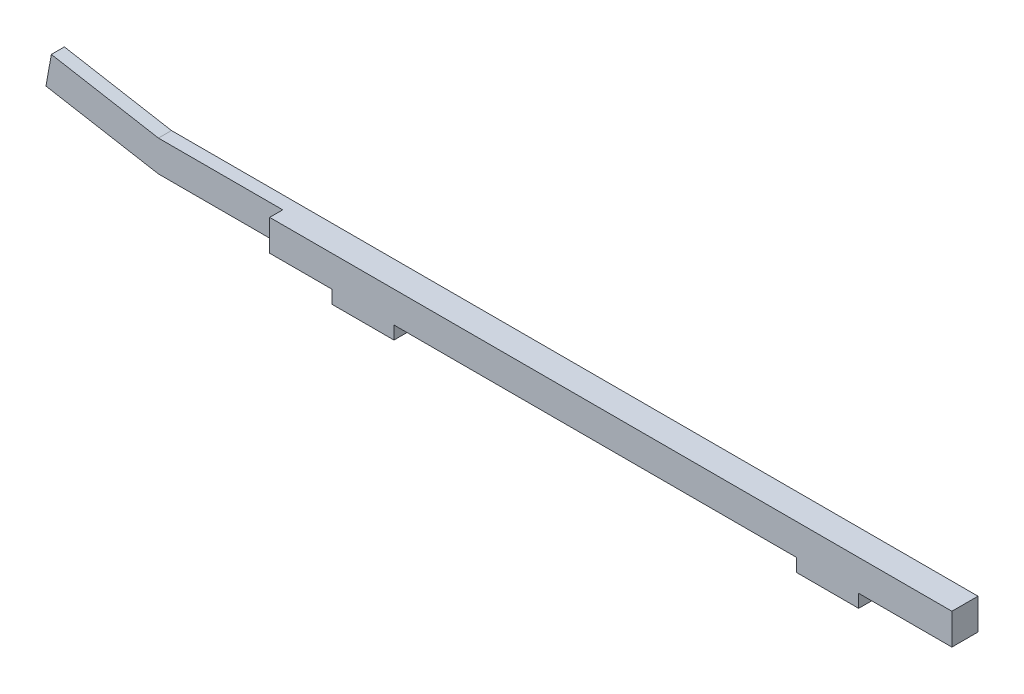
SolidWorks part; units mm, degrees
ref_plane "Front" through (0, 0, 0) normal (0, 0, 1) x (1, 0, 0)
ref_plane "Top" through (0, 0, 0) normal (0, 1, 0) x (1, 0, 0)
ref_plane "Right" through (0, 0, 0) normal (1, 0, 0) x (0, 0, -1)
sketch "Sketch1" plane through (0, 5.334, 0) normal (0, 1, 0) x (1, 0, 0)
  line L0 (266.117, -54.6115) -> (291.517, -54.6115)
  line L1 (76.2, -54.6115) -> (101.6, -54.6115)
  line L2 (76.2, -54.6115) -> (76.2, -65.2795)
  line L3 (76.2, -65.2795) -> (101.6, -65.2795)
  line L4 (101.6, -54.6115) -> (101.6, -65.2795)
  line L5 (266.117, -54.6115) -> (266.117, -65.2795)
  line L6 (266.117, -65.2795) -> (291.517, -65.2795)
  line L7 (291.517, -54.6115) -> (291.517, -65.2795)
  line L8 (380.417, -21.0684) -> (380.417, -97.6337) construction
  line L9 (0, 0) -> (0, -206.442) construction
  line L11 (329.617, -54.6115) -> (0, -54.6115)
  line L12 (329.617, -54.6115) -> (329.617, -65.2795)
  line L13 (329.617, -65.2795) -> (0, -65.2795)
  line L14 (0, -54.6115) -> (0, -65.2795)
  line M10 (0, 0) -> (0, -170.2354)
  dimension "D1" = 25.4
  dimension "D2" = 10.668
  dimension "D4" = 88.9
  dimension "D5" = 76.2
  dimension "D6" = 50.8
  dimension "D3" = 2
extrude "Boss-Extrude1" add sketch "Sketch1" against normal blind 5.334 contours L4 L1 L2 L3 | L7 L0 L5 L6 region at (278.817, 5.334, 59.9455) region at (88.9, 5.334, 59.9455)
extrude "Boss-Extrude2" add sketch "Sketch1<3>" along normal blind 12.7 contours L13 L2 L11 M10 | L4 L1 L2 L3 | L13 L5 L11 L4 | L7 L0 L5 L6 | L11 L14 L13 L12 region at (278.817, 5.334, 59.9455) region at (183.8585, 5.334, 59.9455) region at (88.9, 5.334, 59.9455) region at (38.1, 5.334, 59.9455)
sketch "Sketch1<3>" plane through (0, 5.334, 0) normal (0, 1, 0) x (1, 0, 0) same geometry as "Sketch1"
sketch "Sketch2" plane through (0, 0, 54.6115) normal (0, 0, -1) x (-1, 0, 0)
  line L0 (45.9465, 13.4356) -> (43.7747, 25.7527)
  line L1 (-76.2, 5.334) -> (0, 5.334) construction
  line L13 (0, 5.334) -> (45.9465, 13.4356)
  line L14 (0, 18.034) -> (43.7747, 25.7527)
  line M9 (0, 5.334) -> (0, 18.034)
  dimension "D1" = 10
  dimension "D3" = 44.45
extrude "Dihedral Angle" add sketch "Sketch2" against normal blind 5.334 contours L14 L13 L0 | M9 region at (-22.4347, 15.5886, 54.6115)
sketch "Sketch3" plane through (0, 0, 65.2795) normal (0, 0, 1) x (1, 0, 0)
  line L0 (76.2, 5.334) -> (0, 5.334) construction
  line L1 (0, 18.034) -> (50.8, 18.034)
  line L2 (0, 18.034) -> (0, 5.334)
  line L3 (0, 5.334) -> (50.8, 5.334)
  line L4 (50.8, 18.034) -> (50.8, 5.334)
  dimension "D1" = 50.8
extrude "Cut-Extrude1" cut sketch "Sketch3" against normal blind 5.334
sketch "Build Plans" [suppressed] plane through (0, 0, 65.2795) normal (0, 0, 1) x (1, 0, 0)
  line L0 (0, 18.034) -> (-43.7747, 25.7527) construction
  line L1 (-43.7747, 25.7527) -> (-45.9465, 13.4356) construction
  line L2 (-45.9465, 13.4356) -> (0, 5.334) construction
  line L3 (0, 5.334) -> (50.8, 5.334) construction
  line L4 (291.517, 30.734) -> (329.617, 30.734)
  line L5 (50.8, 18.034) -> (0, 18.034) construction
  line L6 (291.517, 36.068) -> (291.517, 30.734)
  line L7 (50.8, 5.334) -> (76.2, 5.334) construction
  line L8 (76.2, 5.334) -> (76.2, 0) construction
  line L9 (76.2, 0) -> (101.6, 0) construction
  line L10 (101.6, 0) -> (101.6, 5.334) construction
  line L11 (101.6, 5.334) -> (266.117, 5.334) construction
  line L12 (266.117, 5.334) -> (266.117, 0) construction
  line L13 (266.117, 0) -> (291.517, 0) construction
  line L14 (291.517, 0) -> (291.517, 5.334) construction
  line L15 (291.517, 5.334) -> (329.617, 5.334) construction
  line L16 (329.617, 5.334) -> (329.617, 18.034) construction
  line L17 (329.617, 18.034) -> (50.8, 18.034) construction
  line L18 (0, 18.034) -> (-43.7747, 25.7527)
  line L19 (-43.7747, 25.7527) -> (-45.9465, 13.4356)
  line L20 (-45.9465, 13.4356) -> (0, 5.334)
  line L21 (0, 5.334) -> (50.8, 5.334)
  line L22 (266.117, 36.068) -> (291.517, 36.068)
  line L23 (50.8, 18.034) -> (0, 18.034)
  line L24 (266.117, 30.734) -> (266.117, 36.068)
  line L25 (50.8, 5.334) -> (76.2, 5.334)
  line L26 (76.2, 5.334) -> (76.2, 0)
  line L27 (76.2, 0) -> (101.6, 0)
  line L28 (101.6, 0) -> (101.6, 5.334)
  line L29 (101.6, 5.334) -> (266.117, 5.334)
  line L30 (266.117, 5.334) -> (266.117, 0)
  line L31 (266.117, 0) -> (291.517, 0)
  line L32 (291.517, 0) -> (291.517, 5.334)
  line L33 (291.517, 5.334) -> (329.617, 5.334)
  line L34 (329.617, 5.334) -> (329.617, 30.734)
  line L35 (329.617, 18.034) -> (50.8, 18.034)
  line L36 (101.6, 30.734) -> (266.117, 30.734)
  line L37 (101.6, 36.068) -> (101.6, 30.734)
  line L38 (76.2, 36.068) -> (101.6, 36.068)
  line L39 (76.2, 30.734) -> (76.2, 36.068)
  line L40 (50.8, 30.734) -> (76.2, 30.734)
  line L41 (50.8, 30.734) -> (50.8, 18.034)
